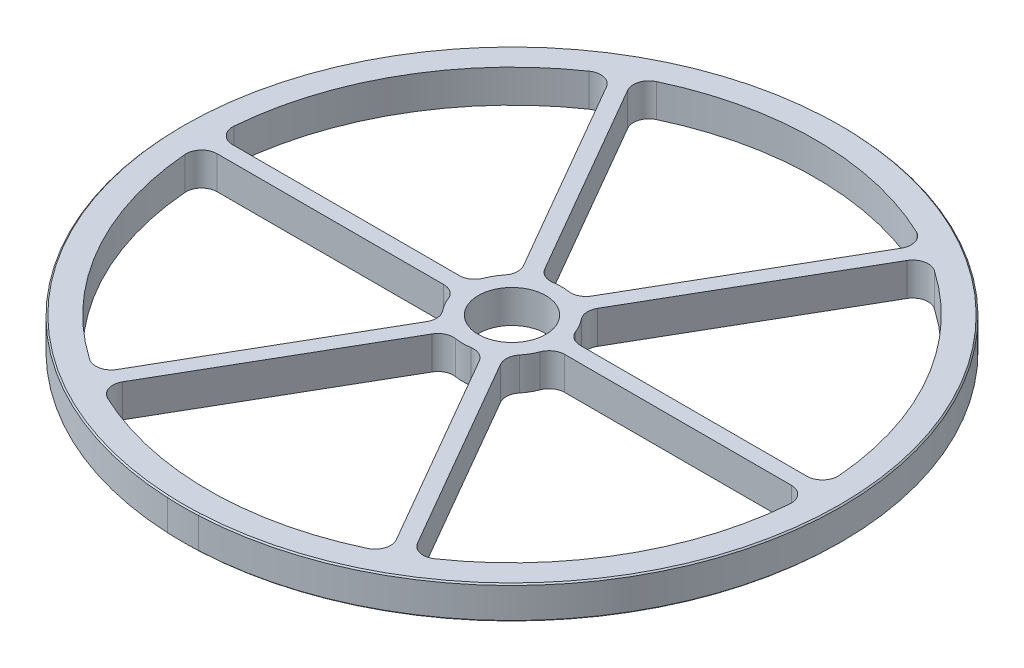
SolidWorks part; units mm, degrees
material "7075-T6, Plate (SS)"
ref_plane "Front Plane" through (0, 0, 0) normal (0, 0, 1) x (1, 0, 0)
ref_plane "Top Plane" through (0, 0, 0) normal (0, 1, 0) x (1, 0, 0)
ref_plane "Right Plane" through (0, 0, 0) normal (1, 0, 0) x (0, 0, -1)
sketch "Sketch1" plane through (0, 0, 0) normal (0, 1, 0) x (1, 0, 0)
  line L0 (0, 0) -> (0, 63.5) construction
  line L2 (-4.5319, 10.8495) -> (-26.3596, 48.6562)
  line L4 (4.5319, 10.8495) -> (26.3596, 48.6562)
  line L11 (7.13, 9.3495) -> (28.9577, 47.1562)
  line L12 (11.6619, 1.5) -> (55.3173, 1.5)
  line L13 (11.6619, -1.5) -> (55.3173, -1.5)
  line L14 (7.13, -9.3495) -> (28.9577, -47.1562)
  line L15 (4.5319, -10.8495) -> (26.3596, -48.6562)
  line L16 (-4.5319, -10.8495) -> (-26.3596, -48.6562)
  line L17 (-7.13, -9.3495) -> (-28.9577, -47.1562)
  line L18 (-11.6619, -1.5) -> (-55.3173, -1.5)
  line L19 (-11.6619, 1.5) -> (-55.3173, 1.5)
  line L20 (-7.13, 9.3495) -> (-28.9577, 47.1562)
  circle A0 centre (0, 0) radius 63.5
  circle A1 centre (0, 0) radius 6.5
  arc A2 (1.4697, 9.3856) -> (-1.4697, 9.3856) centre (0, 0) ccw
  arc A3 (25.0459, 52.8673) -> (-25.0459, 52.8673) centre (0, 0) ccw
  arc A20 (-1.4697, 9.3856) -> (-4.5319, 10.8495) centre (-1.9338, 12.3495) cw
  arc A21 (1.4697, 9.3856) -> (4.5319, 10.8495) centre (1.9338, 12.3495) ccw
  arc A22 (25.0459, 52.8673) -> (26.3596, 48.6562) centre (23.7615, 50.1562) cw
  arc A23 (-25.0459, 52.8673) -> (-26.3596, 48.6562) centre (-23.7615, 50.1562) ccw
  arc A32 (8.863, 3.42) -> (7.3933, 5.9656) centre (0, 0) ccw
  arc A33 (8.863, 3.42) -> (11.6619, 1.5) centre (11.6619, 4.5) ccw
  arc A34 (7.3933, 5.9656) -> (7.13, 9.3495) centre (9.7281, 7.8495) cw
  arc A35 (33.2615, 48.1241) -> (28.9577, 47.1562) centre (31.5557, 45.6562) ccw
  arc A36 (58.3074, 4.7432) -> (33.2615, 48.1241) centre (0, 0) ccw
  arc A37 (58.3074, 4.7432) -> (55.3173, 1.5) centre (55.3173, 4.5) cw
  arc A38 (7.3933, -5.9656) -> (8.863, -3.42) centre (0, 0) ccw
  arc A39 (7.3933, -5.9656) -> (7.13, -9.3495) centre (9.7281, -7.8495) ccw
  arc A40 (8.863, -3.42) -> (11.6619, -1.5) centre (11.6619, -4.5) cw
  arc A41 (58.3074, -4.7432) -> (55.3173, -1.5) centre (55.3173, -4.5) ccw
  arc A42 (33.2615, -48.1241) -> (58.3074, -4.7432) centre (0, 0) ccw
  arc A43 (33.2615, -48.1241) -> (28.9577, -47.1562) centre (31.5557, -45.6562) cw
  arc A44 (-1.4697, -9.3856) -> (1.4697, -9.3856) centre (0, 0) ccw
  arc A45 (-1.4697, -9.3856) -> (-4.5319, -10.8495) centre (-1.9338, -12.3495) ccw
  arc A46 (1.4697, -9.3856) -> (4.5319, -10.8495) centre (1.9338, -12.3495) cw
  arc A47 (25.0459, -52.8673) -> (26.3596, -48.6562) centre (23.7615, -50.1562) ccw
  arc A48 (-25.0459, -52.8673) -> (25.0459, -52.8673) centre (0, 0) ccw
  arc A49 (-25.0459, -52.8673) -> (-26.3596, -48.6562) centre (-23.7615, -50.1562) cw
  arc A50 (-8.863, -3.42) -> (-7.3933, -5.9656) centre (0, 0) ccw
  arc A51 (-8.863, -3.42) -> (-11.6619, -1.5) centre (-11.6619, -4.5) ccw
  arc A52 (-7.3933, -5.9656) -> (-7.13, -9.3495) centre (-9.7281, -7.8495) cw
  arc A53 (-33.2615, -48.1241) -> (-28.9577, -47.1562) centre (-31.5557, -45.6562) ccw
  arc A54 (-58.3074, -4.7432) -> (-33.2615, -48.1241) centre (0, 0) ccw
  arc A55 (-58.3074, -4.7432) -> (-55.3173, -1.5) centre (-55.3173, -4.5) cw
  arc A56 (-7.3933, 5.9656) -> (-8.863, 3.42) centre (0, 0) ccw
  arc A57 (-7.3933, 5.9656) -> (-7.13, 9.3495) centre (-9.7281, 7.8495) ccw
  arc A58 (-8.863, 3.42) -> (-11.6619, 1.5) centre (-11.6619, 4.5) cw
  arc A59 (-58.3074, 4.7432) -> (-55.3173, 1.5) centre (-55.3173, 4.5) ccw
  arc A60 (-33.2615, 48.1241) -> (-58.3074, 4.7432) centre (0, 0) ccw
  arc A61 (-33.2615, 48.1241) -> (-28.9577, 47.1562) centre (-31.5557, 45.6562) cw
  point P44 (-3.3914, 8.874)
  point P47 (3.3914, 8.874)
  point P50 (27.9413, 51.3958)
  point P53 (-27.9413, 51.3958)
  point P72 (0, 0)
  dimension "D1" = 127
  dimension "D2" = 13
  dimension "D3" = 6
  dimension "D4" = 5
  dimension "D7" = 3
  dimension "D8" = 3
  dimension "D6" = 3
  dimension "D5" = 3
extrude "Boss-Extrude3" add sketch "Sketch1" along normal blind 6.35
ref_axis "Axis1" through (0, 6.35, 0) along (0, -1, 0)
ref_plane "Plane3" [suppressed] through (0, 0, 0) normal (0.2756, 0, 0.9613) x (0.9613, 0, -0.2756)
split line "Split Line1" [suppressed]
sketch "Sketch2" [suppressed] plane through (0, 6.35, 0) normal (0, 1, 0) x (1, 0, 0)
  line L0 (0, 0) -> (0, -38.1)
  circle A0 centre (0, 0) radius 38.1 construction
ref_plane "Plane4" [suppressed] through (0, 0, 0) normal (0, 0, 1) x (1, 0, 0)
ref_plane "Plane5" [suppressed] through (0, 0, 38.1) normal (0, 0, 1) x (1, 0, 0)
sketch "Sketch5" [suppressed] plane through (0, 0, 38.1) normal (0, 0, 1) x (1, 0, 0)
  line L5 (38.1, 6.35) -> (-38.1, 6.35) construction
  line L6 (-3, 6.35) -> (3, 6.35)
  line L7 (-3, 6.35) -> (-3, 0)
  line L8 (-3, 0) -> (3, 0)
  line L9 (3, 6.35) -> (3, 0)
  line L10 (-38.1, 0) -> (38.1, 0) construction
  dimension "D1" = 6
split line "Split Line2" [suppressed]
split line "Split Line3" [suppressed]
sketch "Sketch6" plane through (0, 6.35, 0) normal (0, 1, 0) x (1, 0, 0)
  line L0 (0, 0) -> (0, -58.5)
  arc A1 (-25.0459, -52.8673) -> (25.0459, -52.8673) centre (0, 0) ccw construction
ref_plane "Plane7" through (0, 0, 0) normal (0, 0, 1) x (1, 0, 0)
ref_plane "Plane8" through (0, 0, 63.5) normal (0, 0, 1) x (1, 0, 0)
sketch "Sketch7" plane through (0, 0, 63.5) normal (0, 0, 1) x (1, 0, 0)
  line L1 (-3, 6.35) -> (3, 6.35)
  line L2 (-3, 6.35) -> (-3, 0)
  line L3 (-3, 0) -> (3, 0)
  line L4 (3, 6.35) -> (3, 0)
  dimension "D1" = 6.35
  dimension "D2" = 6
split line "Split Line4"
split line "Split Line5" [suppressed]
chamfer "Chamfer2" distance 0.25 angle 45 8 edges at (63.5, 6.35, 0) (0, 6.35, -63.5) (-63.5, 6.35, 0) (0, 6.35, 63.5) (63.5, 0, 0) (0, 0, 63.5) (-63.5, 0, 0) (0, 0, -63.5)
sketch "Sketch9" [suppressed] plane through (0, 6.35, 0) normal (0, 1, 0) x (1, 0, 0)
  circle A7 centre (0, 0) radius 39.25
  circle A8 centre (0, 0) radius 39.25
  circle A10 centre (0, 0) radius 3.5
  circle A11 centre (0, 0) radius 3.5
  circle A13 centre (0, 0) radius 38.25
  circle A14 centre (0, 0) radius 38.25
  circle A16 centre (0, 0) radius 6.5
  circle A17 centre (0, 0) radius 6.5
  circle M6 centre (0, 0) radius 38.25
  circle M7 centre (0, 0) radius 6.5
  dimension "D1" = 1
  dimension "D2" = 3
  dimension "D3" = 0
  dimension "D4" = 0
extrude "Boss-Extrude4" [suppressed] add sketch "Sketch9" against normal up to surface (6.35 mm away) contours A11 M7 | A8 M6
